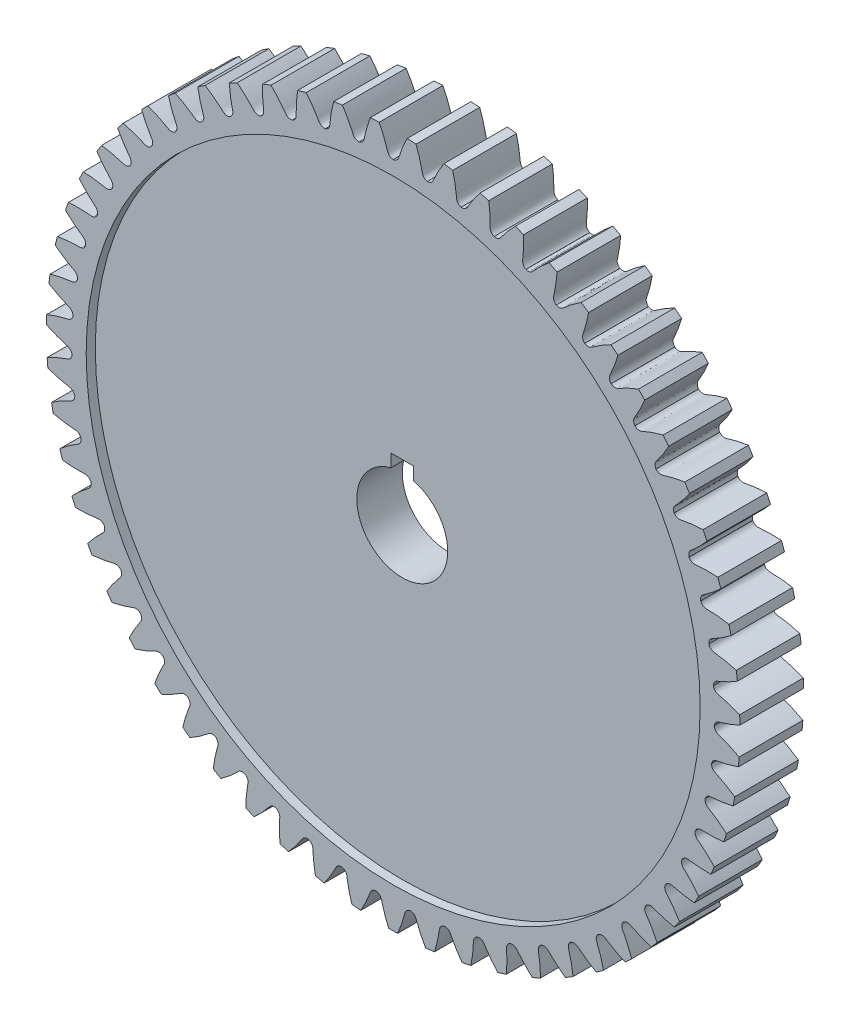
SolidWorks part; units mm, degrees
ref_plane "前视基准面" through (0, 0, 0) normal (0, 0, 1) x (1, 0, 0)
ref_plane "上视基准面" through (0, 0, 0) normal (0, 1, 0) x (1, 0, 0)
ref_plane "右视基准面" through (0, 0, 0) normal (1, 0, 0) x (0, 0, -1)
sketch "草图1" plane through (0, 0, 0) normal (0, 0, 1) x (1, 0, 0)
  circle A0 centre (0, 0) radius 76.25
extrude "凸台-拉伸1" add sketch "草图1" along normal blind 30
ref_axis "基准轴1" through (0, 0, 30) along (0, 0, -1)
sketch "草图2" plane through (0, 0, 0) normal (0, 0, 1) x (1, 0, 0)
  line L0 (0, 0) -> (0, 76.25) construction
  circle A0 centre (0, 0) radius 76.25 construction
  arc A1 (0.01, 70.6249) -> (-0.01, 70.6249) centre (0, 0) ccw
  arc A2 (11.0528, 86.8794) -> (-11.0528, 86.8794) centre (0, 0) ccw
  spline S0 degree 3 poles (0.01, 70.6249) (1.0728, 70.7857) (1.2361, 71.6479) (1.5523, 72.6034) (1.6987, 73.0262) (1.8638, 73.4715) (2.0478, 73.9394) (2.2517, 74.429) (2.4766, 74.9399) (2.7233, 75.4713) (2.9927, 76.0225) (3.2858, 76.593) (3.6034, 77.1818) (3.9463, 77.7884) (4.3154, 78.4118) (4.7115, 79.0512) (5.1354, 79.7059) (5.5878, 80.375) (6.0695, 81.0575) (6.5811, 81.7526) (7.1235, 82.4593) (7.6971, 83.1767) (8.3028, 83.9037) (8.941, 84.6395) (9.8486, 85.6444) (10.5616, 86.3872) (11.0528, 86.8794) knots 0 0 0 0 0.108464 0.129572 0.152074 0.175972 0.201264 0.22795 0.256032 0.285508 0.316379 0.348644 0.382305 0.41736 0.45381 0.491655 0.530894 0.571528 0.613557 0.656981 0.701799 0.748013 0.795621 0.844623 0.895021 1 1 1 1
  spline S1 degree 3 poles (-0.01, 70.6249) (-1.0728, 70.7857) (-1.2361, 71.6479) (-1.5523, 72.6034) (-1.6987, 73.0262) (-1.8638, 73.4715) (-2.0478, 73.9394) (-2.2517, 74.429) (-2.4766, 74.9399) (-2.7233, 75.4713) (-2.9927, 76.0225) (-3.2858, 76.593) (-3.6034, 77.1818) (-3.9463, 77.7884) (-4.3154, 78.4118) (-4.7115, 79.0512) (-5.1354, 79.7059) (-5.5878, 80.375) (-6.0695, 81.0575) (-6.5811, 81.7526) (-7.1235, 82.4593) (-7.6971, 83.1767) (-8.3028, 83.9037) (-8.941, 84.6395) (-9.8486, 85.6444) (-10.5616, 86.3872) (-11.0528, 86.8794) knots 0 0 0 0 0.108464 0.129572 0.152074 0.175972 0.201264 0.22795 0.256032 0.285508 0.316379 0.348644 0.382305 0.41736 0.45381 0.491655 0.530894 0.571528 0.613557 0.656981 0.701799 0.748013 0.795621 0.844623 0.895021 1 1 1 1
extrude "切除-拉伸1" cut sketch "草图2" along normal through all
pattern_circular "阵列(圆周)1" count 59 every 6.102 about axis through (0, 0, 30) along (0, 0, -1) of "切除-拉伸1"
sketch "草图3" plane through (0, 0, 0) normal (0, 0, 1) x (1, 0, 0)
  circle A0 centre (0, 0) radius 73.75 construction
  dimension "Dn" = 147.5
sketch "草图4" plane through (0, 0, 30) normal (0, 0, 1) x (1, 0, 0)
  line L1 (-2.5, 12.5) -> (2.5, 12.5)
  line L2 (-2.5, 12.5) -> (-2.5, 9.6825)
  line L4 (2.5, 12.5) -> (2.5, 9.6825)
  arc A0 (-2.5, 9.6825) -> (2.5, 9.6825) centre (0, 0) ccw
  point P3 (0, 10)
  dimension "D1" = 20
  dimension "D2" = 5
  dimension "D3" = 12.5
extrude "切除-拉伸2" cut sketch "草图4" against normal blind 60
sketch "草图5" plane through (0, 0, 0) normal (0, 0, -1) x (-1, 0, 0)
  circle A0 centre (0, 0) radius 102.3019
extrude "切除-拉伸3" cut sketch "草图5" against normal offset from surface (16 mm away) 14 up to face at (0, 6.1706, 30)
sketch "草图6" plane through (0, 0, 30) normal (0, 0, 1) x (1, 0, 0)
  circle A0 centre (0, 0) radius 67.5
  dimension "D1" = 135
extrude "切除-拉伸4" cut sketch "草图6" against normal blind 2
sketch "草图7" plane through (0, 0, 16) normal (0, 0, -1) x (-1, 0, 0)
  circle A0 centre (0, 0) radius 67.5
  dimension "D1" = 135
extrude "切除-拉伸5" cut sketch "草图7" against normal blind 2
